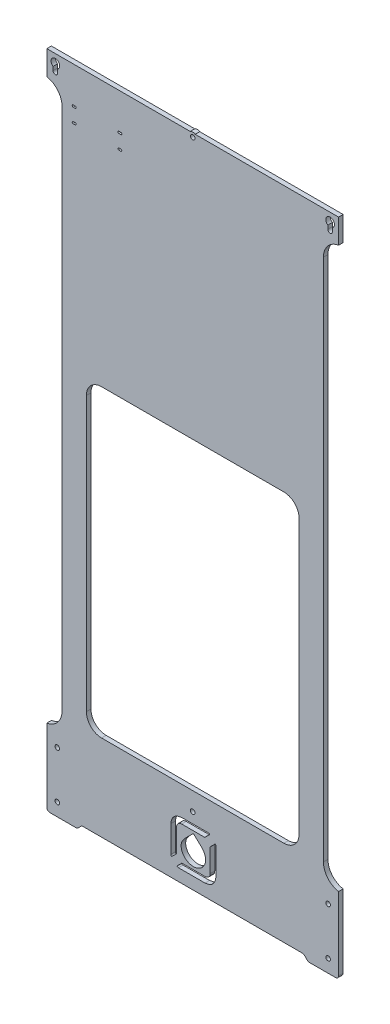
SolidWorks part; units mm, degrees
material "6061-T6 Black anodised"
ref_plane "Front Plane" through (0, 0, 0) normal (0, 0, 1) x (1, 0, 0)
ref_plane "Top Plane" through (0, 0, 0) normal (0, 1, 0) x (1, 0, 0)
ref_plane "Right Plane" through (0, 0, 0) normal (1, 0, 0) x (0, 0, -1)
sketch "Sketch1" plane through (0, 0, 0) normal (0, 0, 1) x (1, 0, 0)
  line L0 (89.02, 0) -> (-89.02, 0) construction
  line L1 (95.92, 394.5) -> (-95.92, 394.5)
  line L2 (95.92, 394.5) -> (95.92, -36.5)
  line L3 (72.92, -36.5) -> (-72.92, -36.5)
  line L4 (-95.92, 394.5) -> (-95.92, -36.5)
  line L5 (95.92, 394.5) -> (-95.92, -36.5) construction
  line L6 (95.92, -36.5) -> (-95.92, 394.5) construction
  line L7 (-90.52, -31) -> (-90.52, -28.5767) construction
  line L8 (-90.32, 384) -> (90.32, 384) construction
  line L9 (0, 384) -> (0, 0) construction
  line L10 (-91.82, 384) -> (-91.82, 386.4233)
  line L11 (-88.82, 384) -> (-88.82, 386.4233)
  line L12 (-90.52, 0) -> (-90.52, 2.4233) construction
  line L13 (-87.52, 0) -> (-87.52, 2.4233) construction
  line L14 (-87.52, -31) -> (-87.52, -28.5767) construction
  line L15 (87.52, -31) -> (87.52, -28.5767) construction
  line L16 (90.52, -31) -> (90.52, -28.5767) construction
  line L17 (87.52, 0) -> (87.52, 2.4233) construction
  line L18 (90.52, 0) -> (90.52, 2.4233) construction
  line L19 (88.82, 384) -> (88.82, 386.4233)
  line L20 (91.82, 384) -> (91.82, 386.4233)
  line L21 (-95.92, -36.5) -> (-95.92, -39.5)
  line L22 (-95.92, -39.5) -> (-75.92, -39.5)
  line L23 (-75.92, -39.5) -> (-72.92, -36.5)
  line L24 (95.92, -36.5) -> (95.92, -39.5)
  line L25 (95.92, -39.5) -> (75.92, -39.5)
  line L26 (75.92, -39.5) -> (72.92, -36.5)
  arc A0 (-90.52, 0) -> (-87.52, 0) centre (-89.02, 0) ccw
  arc A1 (87.52, 0) -> (90.52, 0) centre (89.02, 0) ccw
  arc A2 (-90.52, -31) -> (-87.52, -31) centre (-89.02, -31) ccw
  arc A4 (-91.82, 384) -> (-88.82, 384) centre (-90.32, 384) ccw
  arc A5 (88.82, 384) -> (91.82, 384) centre (90.32, 384) ccw
  arc A6 (-88.82, 386.4233) -> (-91.82, 386.4233) centre (-90.32, 388.8466) ccw
  circle A7 centre (-90.32, 384) radius 2.85 construction
  arc A8 (-87.52, 2.4233) -> (-90.52, 2.4233) centre (-89.02, 4.8466) ccw construction
  circle A9 centre (-89.02, 0) radius 2.85 construction
  arc A10 (-87.52, -28.5767) -> (-90.52, -28.5767) centre (-89.02, -26.1534) ccw construction
  circle A11 centre (-89.02, -31) radius 2.85 construction
  arc A12 (90.52, -28.5767) -> (87.52, -28.5767) centre (89.02, -26.1534) ccw construction
  circle A13 centre (89.02, -31) radius 2.85 construction
  arc A14 (90.52, 2.4233) -> (87.52, 2.4233) centre (89.02, 4.8466) ccw construction
  circle A15 centre (89.02, 0) radius 2.85 construction
  arc A16 (91.82, 386.4233) -> (88.82, 386.4233) centre (90.32, 388.8466) ccw
  circle A17 centre (90.32, 384) radius 2.85 construction
  circle A18 centre (89.02, -31) radius 1.5
  arc A19 (90.52, 0) -> (87.52, 0) centre (89.02, 0) ccw
  arc A20 (-87.52, 0) -> (-90.52, 0) centre (-89.02, 0) ccw
  arc A21 (-87.52, -31) -> (-90.52, -31) centre (-89.02, -31) ccw
  point P0 (0, 179)
  dimension "D4" = 3
  dimension "D7" = 5.6
  dimension "D9" = 5.7
  dimension "D1" = 191.84
  dimension "D2" = 431
  dimension "D3" = 6.9
  dimension "D5" = 31
  dimension "D6" = 5.5
  dimension "D8" = 10.5
  dimension "D10" = 45
  dimension "D11" = 20
  dimension "D12" = 3
extrude "Boss-Extrude1" add sketch "Sketch1" along normal blind 3
sketch "Sketch2" plane through (0, 0, 3) normal (0, 0, 1) x (1, 0, 0)
  line L0 (-95.92, 394.5) -> (-95.92, -39.5) construction
  line L1 (-95.92, 10.5) -> (-85.92, 10.5)
  line L2 (-95.92, 10.5) -> (-95.92, 378.5)
  line L3 (-95.92, 378.5) -> (-85.92, 378.5)
  line L4 (-85.92, 10.5) -> (-85.92, 378.5)
  line L5 (95.92, -39.5) -> (95.92, 394.5) construction
  line L6 (95.92, 10.5) -> (85.92, 10.5)
  line L7 (95.92, 10.5) -> (95.92, 378.5)
  line L8 (95.92, 378.5) -> (85.92, 378.5)
  line L9 (85.92, 10.5) -> (85.92, 378.5)
  line L10 (95.92, 394.5) -> (-95.92, 394.5) construction
  line L11 (-72.92, -36.5) -> (72.92, -36.5) construction
  dimension "D1" = 16
  dimension "D2" = 47
  dimension "D3" = 10
extrude "Cut-Extrude1" cut sketch "Sketch2" against normal through all
fillet "Fillet1" radius 12 4 edges at (85.92, 10.5, 1.5) (-85.92, 10.5, 1.5) (85.92, 378.5, 1.5) (-85.92, 378.5, 1.5)
sketch "Sketch3" plane through (0, 0, 3) normal (0, 0, 1) x (1, 0, 0)
  line L0 (-72.92, -36.5) -> (72.92, -36.5) construction
  line L1 (95.92, 394.5) -> (-95.92, 394.5) construction
  circle A0 centre (0, 8) radius 1.5
  circle A2 centre (0, 392) radius 1.5
  dimension "D2" = 2.5
  dimension "D3" = 3
  dimension "D1" = 44.5
extrude "Cut-Extrude2" cut sketch "Sketch3" against normal through all
sketch "Sketch4" plane through (0, 0, 3) normal (0, 0, 1) x (1, 0, 0)
  line L0 (-85.92, 22.3322) -> (-85.92, 366.6678) construction
  line L1 (-69.92, 220) -> (69.92, 220)
  line L2 (-69.92, 220) -> (-69.92, 20)
  line L3 (-69.92, 20) -> (69.92, 20)
  line L4 (69.92, 220) -> (69.92, 20)
  line L5 (-69.92, 220) -> (69.92, 20) construction
  line L6 (-69.92, 20) -> (69.92, 220) construction
  circle A0 centre (0, 8) radius 1.5 construction
  point P0 (0, 120)
  dimension "D1" = 16
  dimension "D2" = 12
  dimension "D3" = 200
extrude "Cut-Extrude3" cut sketch "Sketch4" against normal through all
fillet "Fillet2" radius 10 4 edges at (69.92, 220, 1.5) (-69.92, 220, 1.5) (69.92, 20, 1.5) (-69.92, 20, 1.5)
sketch "Sketch7" plane through (0, 0, 3) normal (0, 0, 1) x (1, 0, 0)
  line L0 (0, -4.6257) -> (-4.8534, -9.4789)
  line L1 (6.0015, -9.4789) -> (0.8516, -4.6257)
  line L2 (-7.2622, -2.659) -> (7.8165, -2.659)
  line L3 (8.077, -2.549) -> (11.0039, 0.3781)
  line L4 (10.2253, 1.0822) -> (-7.2622, 1.0822)
  line L5 (-14.4113, -6.0673) -> (-14.4098, -23.5545)
  line L6 (-13.7057, -24.3315) -> (-10.7801, -21.4046)
  line L7 (-10.6686, -21.1457) -> (-10.67, -6.0673)
  line L8 (8.1139, -24.8541) -> (-6.9645, -24.8541)
  line L9 (-7.2249, -24.9656) -> (-10.1519, -27.8925)
  line L10 (-9.3733, -28.5967) -> (8.1139, -28.5967)
  line L11 (15.2633, -21.4459) -> (15.2619, -3.9601)
  line L12 (14.5577, -3.1829) -> (11.6308, -6.1099)
  line L13 (11.5207, -6.3688) -> (11.5218, -21.4459)
  spline S0 degree 3 poles (0.4439, -4.4409) (0.3912, -4.446) (0.2828, -4.4565) (0.1286, -4.5203) (0.0426, -4.5908) (0, -4.6257) knots 0 0 0 0 0.322338 0.663828 1 1 1 1
  spline S1 degree 3 poles (-4.8534, -9.4789) (-4.8579, -9.4831) (-4.8667, -9.4912) (-4.8791, -9.5037) (-5.3375, -10.01) (-6.231, -11.0554) (-7.3312, -12.8598) (-7.8887, -15.6825) (-6.8483, -19.2199) (-3.8783, -22.1689) (0.2577, -23.4427) (4.5569, -22.3845) (7.7118, -19.2149) (8.7217, -15.6934) (8.2109, -12.8985) (7.2971, -11.0248) (6.4234, -9.9823) (6.0015, -9.4789) knots 0 0 0 0 0.000489 0.000958 0.001407 0.055151 0.111018 0.168413 0.280621 0.389777 0.490762 0.614387 0.723194 0.83533 0.891393 0.947551 1 1 1 1
  spline S2 degree 3 poles (0.8516, -4.6257) (0.8125, -4.5919) (0.7352, -4.5249) (0.5954, -4.4557) (0.4944, -4.4458) (0.4439, -4.4409) knots 0 0 0 0 0.338885 0.669777 1 1 1 1
  spline S3 degree 3 poles (7.8165, -2.659) (7.8386, -2.6573) (7.882, -2.6541) (7.9472, -2.6464) (7.9964, -2.6204) (8.0324, -2.5949) (8.0557, -2.5715) (8.07, -2.5564) (8.077, -2.549) knots 0 0 0 0 0.227493 0.445972 0.663373 0.787115 0.896006 1 1 1 1
  spline S4 degree 3 poles (11.0039, 0.3781) (11.0329, 0.4173) (11.0909, 0.496) (11.1149, 0.6442) (11.0877, 0.7801) (11.0204, 0.8896) (10.9299, 0.9685) (10.7969, 1.0179) (10.6368, 1.0502) (10.4517, 1.0835) (10.3213, 1.081) (10.25, 1.0825) (10.2377, 1.0831) (10.2294, 1.0825) (10.2253, 1.0822) knots 0 0 0 0 0.104345 0.208931 0.313565 0.397995 0.482811 0.567894 0.701187 0.836715 0.973247 0.982163 0.991064 1 1 1 1
  spline S5 degree 3 poles (-7.2622, 1.0822) (-8.5111, 0.8827) (-10.9772, 0.4887) (-13.8177, -2.3518) (-14.2117, -4.8181) (-14.4113, -6.0673) knots 0 0 0 0 0.336154 0.663772 1 1 1 1
  spline S6 degree 3 poles (-14.4098, -23.5545) (-14.4101, -23.5584) (-14.4107, -23.5663) (-14.4101, -23.5782) (-14.4085, -23.6494) (-14.4116, -23.78) (-14.3778, -23.9655) (-14.348, -24.1263) (-14.2965, -24.2584) (-14.2178, -24.3487) (-14.1086, -24.4167) (-13.9724, -24.4439) (-13.8239, -24.4196) (-13.7451, -24.3609) (-13.7057, -24.3315) knots 0 0 0 0 0.008622 0.017031 0.025643 0.162638 0.298245 0.431901 0.516392 0.601007 0.685957 0.790142 0.895037 1 1 1 1
  spline S7 degree 3 poles (-10.7801, -21.4046) (-10.7711, -21.3953) (-10.7536, -21.3772) (-10.7264, -21.3501) (-10.6977, -21.3146) (-10.6778, -21.2655) (-10.6682, -21.2062) (-10.6685, -21.1664) (-10.6686, -21.1457) knots 0 0 0 0 0.131285 0.25763 0.390972 0.594165 0.788898 1 1 1 1
  spline S8 degree 3 poles (-10.67, -6.0673) (-10.5818, -5.4634) (-10.4093, -4.283) (-9.0474, -2.92) (-7.8666, -2.7474) (-7.2622, -2.659) knots 0 0 0 0 0.33841 0.661392 1 1 1 1
  spline S9 degree 3 poles (-6.9645, -24.8541) (-6.9836, -24.8548) (-7.0187, -24.8562) (-7.0727, -24.8646) (-7.117, -24.885) (-7.157, -24.9087) (-7.1915, -24.9347) (-7.2134, -24.955) (-7.2249, -24.9656) knots 0 0 0 0 0.196746 0.361608 0.557262 0.692766 0.839563 1 1 1 1
  spline S10 degree 3 poles (-10.1519, -27.8925) (-10.1809, -27.9318) (-10.2389, -28.0105) (-10.2629, -28.1587) (-10.2357, -28.2947) (-10.1681, -28.4041) (-10.0777, -28.4828) (-9.9452, -28.5327) (-9.7851, -28.5653) (-9.6, -28.5955) (-9.4695, -28.601) (-9.3981, -28.5958) (-9.3857, -28.5965) (-9.3774, -28.5966) (-9.3733, -28.5967) knots 0 0 0 0 0.104385 0.20895 0.313569 0.398093 0.483012 0.567612 0.700915 0.836485 0.973043 0.982112 0.991066 1 1 1 1
  spline S11 degree 3 poles (8.1139, -28.5967) (9.3629, -28.3971) (11.8293, -28.0028) (14.6704, -25.162) (15.064, -22.6952) (15.2633, -21.4459) knots 0 0 0 0 0.336157 0.663806 1 1 1 1
  spline S12 degree 3 poles (15.2619, -3.9601) (15.2622, -3.956) (15.2628, -3.9477) (15.2621, -3.9352) (15.2606, -3.8638) (15.2632, -3.7334) (15.2298, -3.5483) (15.198, -3.3882) (15.148, -3.2557) (15.0694, -3.1653) (14.9599, -3.0977) (14.8239, -3.0705) (14.6754, -3.0949) (14.597, -3.1536) (14.5577, -3.1829) knots 0 0 0 0 0.008953 0.017947 0.027021 0.163491 0.298949 0.432165 0.516776 0.601601 0.686035 0.790672 0.895263 1 1 1 1
  spline S13 degree 3 poles (11.6308, -6.1099) (11.6212, -6.1191) (11.6023, -6.1372) (11.5737, -6.165) (11.5433, -6.1982) (11.5265, -6.2477) (11.5219, -6.3062) (11.5211, -6.3471) (11.5207, -6.3688) knots 0 0 0 0 0.134582 0.264928 0.404991 0.586048 0.77989 1 1 1 1
  spline S14 degree 3 poles (11.5218, -21.4459) (11.4339, -22.05) (11.262, -23.2307) (9.8992, -24.5934) (8.7183, -24.7658) (8.1139, -24.8541) knots 0 0 0 0 0.338406 0.661372 1 1 1 1
extrude "Cut-Extrude6" cut sketch "Sketch7" against normal through all
sketch "Sketch8" plane through (0, 0, 3) normal (0, 0, 1) x (1, 0, 0)
  line L0 (95.92, 394.5) -> (-95.92, 394.5) construction
  line L1 (-1.6583, 394.5) -> (1.6583, 394.5)
  arc A0 (1.6583, 394.5) -> (-1.6583, 394.5) centre (0, 392) ccw
  dimension "D1" = 3
extrude "Boss-Extrude2" add sketch "Sketch8" against normal up to surface (3 mm away) up to face at (5.0456, -18.6663, 0)
sketch "Sketch9" plane through (0, 0, 3) normal (0, 0, 1) x (1, 0, 0)
  line L0 (-1.6583, 394.5) -> (-95.92, 394.5) construction
  line L1 (-85.92, 22.3322) -> (-85.92, 366.6678) construction
  line L2 (-78.57, 370.5) -> (-77.27, 370.5) construction
  line L3 (-78.57, 371.15) -> (-77.27, 371.15)
  line L4 (-78.57, 369.85) -> (-77.27, 369.85)
  line L5 (-78.57, 361) -> (-77.27, 361) construction
  line L6 (-78.57, 361.65) -> (-77.27, 361.65)
  line L7 (-78.57, 360.35) -> (-77.27, 360.35)
  line L8 (-48.57, 370.5) -> (-47.27, 370.5) construction
  line L9 (-48.57, 371.15) -> (-47.27, 371.15)
  line L10 (-48.57, 369.85) -> (-47.27, 369.85)
  line L11 (-48.57, 361) -> (-47.27, 361) construction
  line L12 (-48.57, 361.65) -> (-47.27, 361.65)
  line L13 (-48.57, 360.35) -> (-47.27, 360.35)
  line L14 (-78.57, 361) -> (-48.57, 361) construction
  line L15 (-47.92, 370.5) -> (-77.92, 361) construction
  circle A0 centre (-77.92, 370.5) radius 0.65 construction
  circle A1 centre (-77.92, 361) radius 0.65 construction
  arc A2 (-78.57, 371.15) -> (-78.57, 369.85) centre (-78.57, 370.5) ccw
  arc A3 (-77.27, 369.85) -> (-77.27, 371.15) centre (-77.27, 370.5) ccw
  arc A4 (-78.57, 361.65) -> (-78.57, 360.35) centre (-78.57, 361) ccw
  arc A5 (-77.27, 360.35) -> (-77.27, 361.65) centre (-77.27, 361) ccw
  arc A6 (-48.57, 371.15) -> (-48.57, 369.85) centre (-48.57, 370.5) ccw
  arc A7 (-47.27, 369.85) -> (-47.27, 371.15) centre (-47.27, 370.5) ccw
  arc A8 (-48.57, 361.65) -> (-48.57, 360.35) centre (-48.57, 361) ccw
  arc A9 (-47.27, 360.35) -> (-47.27, 361.65) centre (-47.27, 361) ccw
  point P10 (-77.92, 370.5)
  point P15 (-77.92, 361)
  point P25 (-47.92, 370.5)
  point P30 (-47.92, 361)
  dimension "D1" = 1.3
  dimension "D3" = 24
  dimension "D4" = 8
  dimension "D2" = 9.5
  dimension "D6" = 30
  dimension "D5" = 2
extrude "Cut-Extrude7" cut sketch "Sketch9" against normal through all
fillet "Fillet3" radius 2 6 edges at (72.92, -36.5, 1.5) (75.92, -39.5, 1.5) (95.92, -39.5, 1.5) (-72.92, -36.5, 1.5) (-75.92, -39.5, 1.5) (-95.92, -39.5, 1.5)
sketch "Sketch10" plane through (0, 0, 3) normal (0, 0, 1) x (1, 0, 0)
  line L0 (-95.92, 10.5) -> (-95.92, -37.5) construction
  line L1 (-88.02, 7.7) -> (-81.17, 7.7)
  line L2 (-88.02, 7.7) -> (-88.02, -3.5)
  line L3 (-88.02, -3.5) -> (-81.17, -3.5)
  line L4 (-81.17, 7.7) -> (-81.17, -3.5)
  line L5 (-88.02, -23.3) -> (-88.02, -34.5)
  line L6 (-88.02, -34.5) -> (-81.17, -34.5)
  line L7 (-81.17, -23.3) -> (-81.17, -34.5)
  line L8 (-88.02, -23.3) -> (-81.17, -23.3)
  circle A0 centre (0, 8) radius 1.5 construction
  point P4 (-81.17, 0)
  dimension "D5" = 8
  dimension "D1" = 6.85
  dimension "D2" = 11.2
  dimension "D3" = 7.9
  dimension "D4" = 3.5
  dimension "D6" = 2
extrude "Cut-Extrude8" [suppressed] cut sketch "Sketch10" against normal through all
chamfer "Chamfer1" [suppressed] distance 3 angle 10
chamfer "Chamfer2" [suppressed] distance 2 angle 45
mirror "Mirror1" [suppressed] about plane through (0, 0, 0) normal (1, 0, 0)
